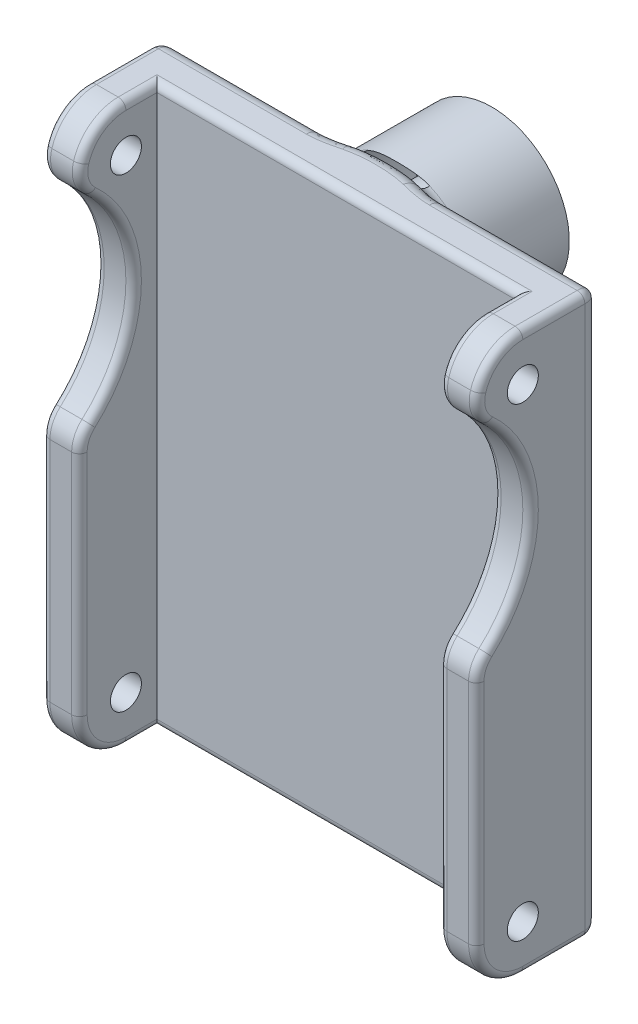
SolidWorks part; units mm, degrees
material "ABS"
ref_plane "前视基准面" through (0, 0, 0) normal (0, 0, 1) x (1, 0, 0)
ref_plane "上视基准面" through (0, 0, 0) normal (0, 1, 0) x (1, 0, 0)
ref_plane "右视基准面" through (0, 0, 0) normal (1, 0, 0) x (0, 0, -1)
other "Configuration Table"
sketch "草图1" plane through (0, 0, 0) normal (0, 0, 1) x (1, 0, 0)
  line L1 (-14, 18) -> (14, 18)
  line L2 (-14, 18) -> (-14, -18)
  line L3 (-14, -18) -> (14, -18)
  line L4 (14, 18) -> (14, -18)
  line L5 (-14, 18) -> (14, -18) construction
  line L6 (-14, -18) -> (14, 18) construction
  point P4 (0, 0)
  dimension "D1" = 36
  dimension "D2" = 28
extrude "凸台-拉伸1" add sketch "草图1" along normal blind 8
sketch "草图2" plane through (0, 0, 8) normal (0, 0, 1) x (1, 0, 0)
  line L1 (-11.6, 18) -> (11.6, 18)
  line L2 (-11.6, 18) -> (-11.6, -18)
  line L3 (-11.6, -18) -> (11.6, -18)
  line L4 (11.6, 18) -> (11.6, -18)
  line L5 (-11.6, 18) -> (11.6, -18) construction
  line L6 (-11.6, -18) -> (11.6, 18) construction
  line L7 (-14, -18) -> (14, -18) construction
  line L10 (0, 18) -> (0, -18) construction
  line L11 (14, 18) -> (-14, 18) construction
  point P4 (0, 0)
  dimension "D1" = 23.2
extrude "切除-拉伸1" cut sketch "草图2" against normal offset from surface (5 mm away) 3 up to face at (0, 0, 0)
sketch "草图3" plane through (0, 0, 0) normal (0, 0, -1) x (-1, 0, 0)
  line L0 (0, 18) -> (0, -18) construction
  line L1 (-14, 18) -> (14, 18) construction
  line L2 (14, -18) -> (-14, -18) construction
  line L3 (-14, 0) -> (14, 0) construction
  line L4 (-14, -18) -> (-14, 18) construction
  line L5 (14, 18) -> (14, -18) construction
  circle A0 centre (0, 12.5) radius 2.5
  circle A1 centre (0, 12.5) radius 5
  circle A2 centre (0, -12.5) radius 2.5
  circle A3 centre (0, -12.5) radius 5
  dimension "D1" = 5
  dimension "D2" = 10
  dimension "D3" = 25
extrude "凸台-拉伸2" add sketch "草图3" along normal blind 7
sketch "草图4" plane through (14, 0, 0) normal (1, 0, 0) x (0, 0, -1)
  line L0 (-5, -18) -> (-5, 26.9187) construction
  line L1 (-8, -18) -> (0, -18) construction
  line L2 (-8, 0) -> (0, 0) construction
  line L3 (-8, -18) -> (-8, 18) construction
  line L4 (0, -18) -> (0, 18) construction
  line L5 (-3, -18) -> (-3, 18) construction
  line L6 (-3, -18) -> (-3, 18) construction
  circle A0 centre (-5, -15) radius 1
  circle A1 centre (-5, 15) radius 1
  dimension "D2" = 2
  dimension "D3" = 30
  dimension "D1" = 2
extrude "切除-拉伸2" cut sketch "草图4" against normal through all
sketch "草图5" plane through (14, 0, 0) normal (1, 0, 0) x (0, 0, -1)
  line L2 (-3, 18) -> (-3, -18) construction
  line L3 (-3, 18) -> (-3, -18) construction
  circle A0 centre (-13, 7.5) radius 8.5
  circle A1 centre (-5, 15) radius 1 construction
  dimension "D1" = 10
  dimension "D2" = 17
  dimension "D3" = 7.5
extrude "切除-拉伸3" cut sketch "草图5" against normal blind 40
fillet "圆角1" radius 3 4 edges at (-12.8, 18, 8) (12.8, 18, 8) (-12.8, -18, 8) (12.8, -18, 8)
fillet "圆角2" radius 2 4 edges at (-12.8, 0.6261, 8) (-12.8, 14.3739, 8) (12.8, 0.6261, 8) (12.8, 14.3739, 8)
fillet "圆角3" radius 1 2 edges at (5, 12.5, 0) (5, -12.5, 0)
fillet "圆角4" radius 1 8 edges at (-8.199, 18, 0) (0, 18, 0) (-8.199, -18, 0) (14, 0, 0) (8.199, 18, 0) (-14, 0, 0) (8.199, -18, 0) (0, -18, 0)
fillet "圆角5" radius 0.5 38 edges at (-13.7071, 17.7071, 0.2929) (-14, 18, 3) (-14, 17.4076, 6.7898) (-14, 14.7514, 7.8842) (-14, 7.4769, 4.5) (-14, 0.4903, 7.8257) (-14, -7.6631, 8) (-14, -17.1213, 7.1213) (-13.7071, -17.7071, 0.2929) (13.7071, 17.7071, 0.2929) (14, 18, 3) (14, 17.4076, 6.7898) (14, 14.7514, 7.8842) (14, 7.4769, 4.5) (14, 0.4903, 7.8257) (14, -7.6631, 8) (14, -17.1213, 7.1213) (13.7071, -17.7071, 0.2929) (0, -18, 3) (0, 18, 3) (-14, -18, 3) (14, -18, 3) (11.6, 18, 4) (11.6, 17.4076, 6.7898) (11.6, 14.7514, 7.8842) (11.6, 7.4769, 4.5) (11.6, 0.4903, 7.8257) (11.6, -7.6631, 8) (11.6, -17.1213, 7.1213) (-11.6, 18, 4) (-11.6, 17.4076, 6.7898) (-11.6, 14.7514, 7.8842) (-11.6, 7.4769, 4.5) (-11.6, 0.4903, 7.8257) (-11.6, -7.6631, 8) (-11.6, -17.1213, 7.1213) (11.6, -18, 4) (-11.6, -18, 4)
